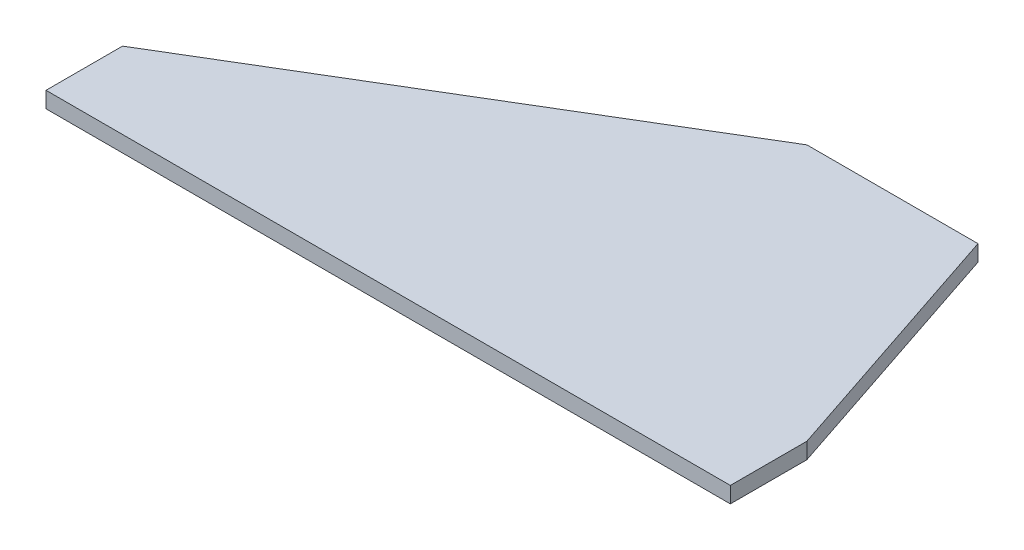
SolidWorks part; units mm, degrees
ref_plane "Front Plane" through (0, 0, 0) normal (0, 0, 1) x (1, 0, 0)
ref_plane "Top Plane" through (0, 0, 0) normal (0, 1, 0) x (1, 0, 0)
ref_plane "Right Plane" through (0, 0, 0) normal (1, 0, 0) x (0, 0, -1)
sketch "Sketch1" plane through (0, 0, 0) normal (0, 1, 0) x (1, 0, 0)
  line L0 (0, 0) -> (0, 22.733)
  line L1 (0, 22.733) -> (127, 98.933)
  line L2 (127, 98.933) -> (177.8, 98.933)
  line L3 (177.8, 98.933) -> (203.2, 22.733)
  line L4 (203.2, 22.733) -> (203.2, 0)
  line L5 (203.2, 0) -> (0, 0)
  line L6 (0, 22.733) -> (0, 98.933) construction
  line L7 (0, 98.933) -> (127, 98.933) construction
  dimension "D1" = 203.2
  dimension "D2" = 22.733
  dimension "D3" = 50.8
  dimension "D4" = 76.2
  dimension "D5" = 127
extrude "Boss-Extrude1" add sketch "Sketch1" along normal blind 2.3813 and the other way blind 2.3813 contours L3 L4 L5 L0 L1 L2
equation "\"Root Chord\"= 8"
equation "\"Tip Chord\"=2"
equation "\"Height\"=3"
equation "\"Sweep Length\"=5"
equation "\"Fin Thickness\"= 3 / 16"
equation "\"Bevel Depth\"= 1 / 16"
equation "\"Bevel Width\"= 1 / 4"
equation "\"Tab Height\"=0.895"
equation "\"D2@Sketch1\"=\"Tab Height\""
equation "\"D4@Sketch1\"=\"Height\""
equation "\"D5@Sketch1\"=\"Sweep Length\""
equation "\"D3@Sketch1\"=\"Tip Chord\""
equation "\"D1@Sketch1\"=\"Root Chord\""
equation "\"D1@Boss-Extrude1\"=\"Fin Thickness\"/2"
equation "\"D2@Boss-Extrude1\"=\"Fin Thickness\"/2"
equation "\"D1@Chamfer2\"=\"Bevel Depth\""
equation "\"D3@Chamfer2\"=\"Bevel Width\""
